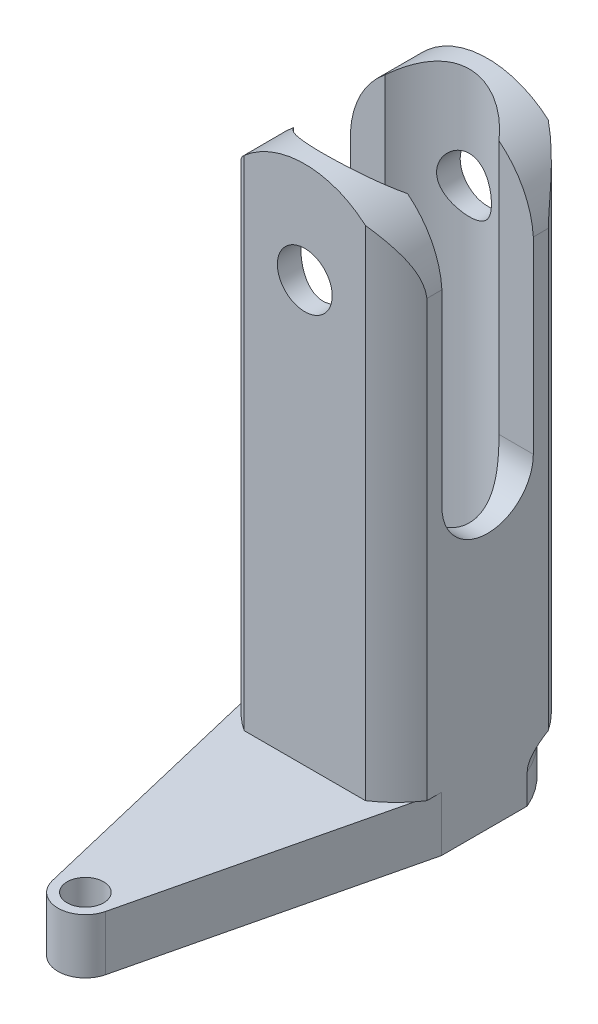
SolidWorks part; units mm, degrees
material "6061 Alloy"
ref_plane "Front Plane" through (0, 0, 0) normal (0, 0, 1) x (1, 0, 0)
ref_plane "Top Plane" through (0, 0, 0) normal (0, 1, 0) x (1, 0, 0)
ref_plane "Right Plane" through (0, 0, 0) normal (1, 0, 0) x (0, 0, -1)
sketch "Sketch1" plane through (0, 0, 0) normal (0, 1, 0) x (1, 0, 0)
  circle A0 centre (0, 0) radius 2
  circle A1 centre (0, 0) radius 6
  dimension "D1" = 4
extrude "Boss-Extrude1" add sketch "Sketch1" along normal blind 28.5
ref_plane "Plane1" through (0, -3, 0) normal (0, -1, 0) x (-1, 0, 0)
sketch "Sketch2" plane through (0, -3, 0) normal (0, -1, 0) x (-1, 0, 0)
  line L0 (-1.459, -17.3485) -> (-5.3005, -1.2661)
  line L5 (0, 13.1723) -> (0, -13.1723) construction
  line L6 (1.459, -17.3485) -> (5.3005, -1.2661)
  circle A0 centre (0, 0) radius 2
  arc A1 (5.3005, -1.2661) -> (-5.3005, -1.2661) centre (0, 0) ccw
  circle A2 centre (0, 0) radius 6 construction
  circle A3 centre (0, -17) radius 1
  arc A4 (-1.459, -17.3485) -> (1.459, -17.3485) centre (0, -17) ccw
  point P4 (0, -6)
  dimension "D1" = 17
extrude "Boss-Extrude2" add sketch "Sketch2" against normal up to surface (3 mm away) up to face at (0, 0, 6)
sketch "Sketch3" plane through (0, 28.5, 0) normal (0, 1, 0) x (1, 0, 0)
  line L1 (-3.1218, -2.5) -> (-3.1225, -2.5)
  line L3 (-3.1218, 2.5) -> (-3.1225, 2.5)
  line L8 (3.1225, 2.5) -> (3.1293, 2.5)
  line L9 (3.1225, -2.5) -> (3.1293, -2.5)
  circle A5 centre (0, 0) radius 4
  point P0 (0, 0)
  dimension "D1" = 5
extrude "Cut-Extrude1" cut sketch "Sketch3" against normal blind 23 contours A5 region at (3.6675, 28.5, 1.2873)
sketch "Sketch4" plane through (0, 0, 0) normal (0, 1, 0) x (1, 0, 0)
  line L0 (-6.5, 6.5) -> (6.5, 6.5)
  line L1 (-5, -5) -> (5, -5)
  line L2 (-5, -5) -> (-5, 5)
  line L3 (-5, 5) -> (5, 5)
  line L4 (5, -5) -> (5, 5)
  line L5 (-5, -5) -> (5, 5) construction
  line L6 (-5, 5) -> (5, -5) construction
  line L7 (6.5, -6.5) -> (6.5, 6.5)
  line L8 (-6.5, -6.5) -> (6.5, -6.5)
  line L9 (-6.5, -6.5) -> (-6.5, 6.5)
  line L10 (-3.5, 3.5) -> (3.5, 3.5)
  line L11 (3.5, -3.5) -> (3.5, 3.5)
  line L12 (-3.5, -3.5) -> (3.5, -3.5)
  line L13 (-3.5, -3.5) -> (-3.5, 3.5)
  point P0 (0, 0)
  arc M4 (4.7172, -3.7078) -> (-4.7172, -3.7078) centre (0, 0) cw
  line M5 (-4.7172, -3.7078) -> (-1.459, -17.3485)
  line M7 (1.459, -17.3485) -> (4.7172, -3.7078)
  dimension "D1" = 10
  dimension "D2" = 10
  dimension "D3" = 1.5
  dimension "D4" = 1.5
extrude "Cut-Extrude2" cut sketch "Sketch4" along normal through all contours L9 L8 L7 L0 L4 L1 L2 L3 M5 M4 M7 | L8 L1 M5 M7 M4 | L1 M4 region at (0, 0, -6.3162) region at (-4.1424, 0, 5.7292) region at (0, 0, 5.403)
sketch "Sketch8" plane through (0, 0, 5) normal (0, 0, 1) x (1, 0, 0)
  line L0 (-5, 0) -> (-5, 28.5) construction
  line L1 (5, 0) -> (5, 28.5) construction
  line L2 (-5, 23.7912) -> (-6.4415, 23.7912)
  line L3 (-6.4415, 23.7912) -> (-6.4415, 29.3856)
  line L4 (-6.4415, 29.3856) -> (5.9884, 29.3856)
  line L5 (5, 23.7912) -> (5.9884, 23.7912)
  line L6 (5.9884, 23.7912) -> (5.9884, 29.3856)
  arc A0 (-5, 23.7912) -> (5, 23.7912) centre (0, 23.491) cw
extrude "Cut-Extrude5" cut sketch "Sketch8" against normal through all contours L3 L4 L6 L5 A0 L2
sketch "Sketch9" plane through (-5, 0, 0) normal (-1, 0, 0) x (0, 0, 1)
  line L1 (-2.5, 28.5) -> (2.5, 28.5)
  line L5 (-2.5, 28.5) -> (2.5, 28.5)
  line L6 (-2.5, 28.5) -> (-2.5, 13.5)
  line L8 (2.5, 28.5) -> (2.5, 13.5)
  line L9 (-5, 0) -> (-5, 27.2447) construction
  line L11 (-3.9999, 28.5) -> (-5, 28.5) construction
  arc A0 (-2.5, 13.5) -> (2.5, 13.5) centre (0, 13.5) ccw
  line M3 (3.3166, 23.7912) -> (-3.3166, 23.7912)
  dimension "D1" = 5
  dimension "D2" = 2.5
  dimension "D3" = 15
extrude "Cut-Extrude6" cut sketch "Sketch9" against normal through all contours L8 L1 L6 M3 | L6 A0 L8 M3 region at (-5, 26.1456, 0) region at (-5, 17.6511, 0)
sketch "Sketch10" plane through (0, 0, 0) normal (0, 1, 0) x (1, 0, 0)
  line L0 (-5, 3.3166) -> (-5, -3.3166)
  line L1 (-5, -3.3166) -> (-6.3874, -3.3166)
  line L2 (-6.3874, -3.3166) -> (-6.3874, 5)
  line L3 (-5, 5) -> (5, 5)
  line L4 (5, 5) -> (5, -3.3166)
  line L5 (5, -3.3166) -> (6.9833, -3.3166)
  line L6 (6.9833, -3.3166) -> (6.9833, 6.8209)
  line L7 (6.9833, 6.8209) -> (-6.3874, 6.8209)
  line L8 (-6.3874, 6.8209) -> (-6.3874, 5)
  line L9 (-5, 3.3166) -> (-5, 5)
extrude "Cut-Extrude7" cut sketch "Sketch10" against normal through all contours L7 L8 L2 L1 L0 L9 L3 L4 L5 L6
sketch "Sketch11" plane through (0, 0, 5) normal (0, 0, 1) x (1, 0, 0)
  line L0 (5, -3) -> (1.459, -3) construction
  circle A0 centre (0, 23) radius 1.5
  dimension "D1" = 26
extrude "Cut-Extrude8" cut sketch "Sketch11" against normal through all
fillet "Fillet1" radius 2 2 edges at (3.8534, 0, -3.8534) (-3.8534, 0, -3.8534)
